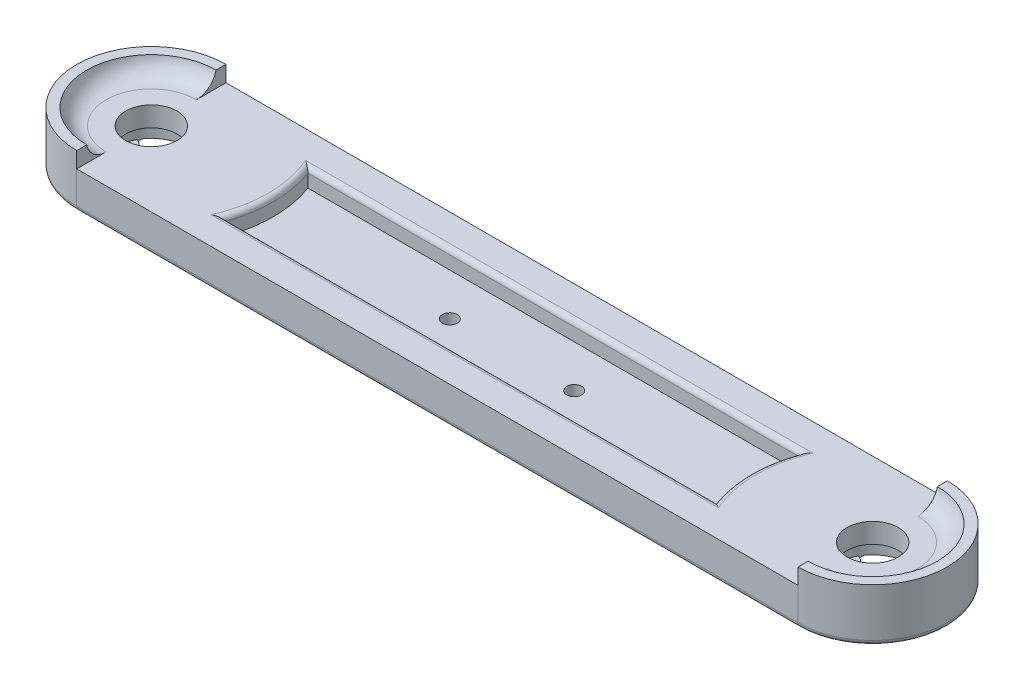
SolidWorks part; units mm, degrees
ref_plane "Alzado" through (0, 0, 0) normal (0, 0, 1) x (1, 0, 0)
ref_plane "Planta" through (0, 0, 0) normal (0, 1, 0) x (1, 0, 0)
ref_plane "Vista lateral" through (0, 0, 0) normal (1, 0, 0) x (0, 0, -1)
sketch "Croquis1" plane through (0, 0, 0) normal (0, 1, 0) x (1, 0, 0)
  line L0 (72.5, 0) -> (-72.5, 0) construction
  line L1 (-72.5, 15) -> (-72.5, -15) construction
  line L2 (-72.5, 0) -> (-80, 12.9904) construction
  line L3 (-72.5, 0) -> (-80, -12.9904) construction
  line L4 (0, 0) -> (0, 15) construction
  line L5 (-72.5, 15) -> (72.5, 15)
  line L6 (-72.5, -15) -> (72.5, -15)
  circle A0 centre (-72.5, 0) radius 15
  circle A2 centre (-72.5, 0) radius 5.15
  circle A3 centre (72.5, 0) radius 15
  circle A4 centre (72.5, 0) radius 5.15
  point P4 (0, 0)
  dimension "D3" = 30
  dimension "D4" = 10.3
  dimension "D1" = 145
  dimension "D2" = 30
  dimension "D5" = 30
  dimension "D6" = 15
extrude "Saliente-Extruir1" add sketch "Croquis1" along normal blind 7.5 contours A0 A2 | L6 A3 L5 A0 | A3 A4 region at (0, 0, 0) region at (-62.1934, 0, -10.3066) region at (82.8066, 0, -10.3066)
sketch "Croquis2" plane through (0, 0, 0) normal (0, -1, 0) x (1, 0, 0)
  line L0 (-72.5, 5.15) -> (-72.5, -5.15) construction
  line L1 (-72.5, 0) -> (-72.5, 5.15) construction
  line L2 (-72.5, 0) -> (-72.5, -5.15) construction
  line L3 (-72.5, 0) -> (-72.5, -5.15) construction
  line L4 (-72.5, 0) -> (-72.5, 5.15) construction
  line L5 (-72.5, 5.15) -> (-72.5, 7.5)
  line L6 (-72.5, 5.15) -> (-72.5, 7.5)
  line L7 (-72.5, -5.15) -> (-72.5, -7.5)
  line L8 (-72.5, -5.15) -> (-72.5, -7.5)
  line L9 (0, 0) -> (0, 15) construction
  line L10 (-72.5, 15) -> (72.5, 15) construction
  line L11 (72.5, -5.15) -> (72.5, -7.5)
  line L12 (72.5, -5.15) -> (72.5, -7.5)
  line L13 (72.5, 5.15) -> (72.5, 7.5)
  line L14 (72.5, 5.15) -> (72.5, 7.5)
  circle A0 centre (-72.5, 0) radius 5.15 construction
  circle A1 centre (-72.5, 0) radius 5.15
  arc A2 (-72.5, 7.5) -> (-72.5, -7.5) centre (-72.5, 0) ccw
  arc A3 (-72.5, -7.5) -> (-72.5, 7.5) centre (-72.5, 0) ccw
  arc A4 (72.5, -7.5) -> (72.5, 7.5) centre (72.5, 0) cw
  circle A5 centre (72.5, 0) radius 5.15
  arc A6 (72.5, 7.5) -> (72.5, -7.5) centre (72.5, 0) cw
  circle M6 centre (-72.5, 0) radius 5.15
  circle M11 centre (72.5, 0) radius 5.15
  dimension "D3" = 15
  dimension "D1" = 0
  dimension "D2" = 0
extrude "Cortar-Extruir1" cut sketch "Croquis2" against normal blind 3.5 contours L6 A2 L7 M6 | L8 A3 L5 M6 | A4 L12 L13 M11 | A6 L14 L11 M11 region at (-77.8177, 0, 0) region at (-72.3323, 0, 6.325) region at (76.2602, 0, -3.7602) region at (72.3323, 0, -6.325)
sketch "Croquis3" plane through (0, 7.5, 0) normal (0, 1, 0) x (1, 0, 0)
  line L0 (-87.5, 0) -> (87.5, 0) construction
  line L1 (-17.5, 25) -> (-23.5102, 25)
  line L2 (-17.5, -25) -> (-23.5102, -25)
  line L3 (0, 0) -> (0, 30) construction
  line L4 (17.5, -25) -> (23.5102, -25)
  line L5 (12.5, -30) -> (-12.5, -30)
  line L6 (17.5, -25) -> (17.5, 25)
  line L7 (12.5, 30) -> (-12.5, 30)
  line L8 (-17.5, -25) -> (-17.5, 25)
  line L9 (17.5, -30) -> (-17.5, 30) construction
  line L10 (17.5, 30) -> (-17.5, -30) construction
  line L11 (17.5, 25) -> (23.5102, 25)
  arc A0 (-72.5, 15) -> (-72.5, -15) centre (-72.5, 0) ccw construction
  arc A1 (72.5, -15) -> (72.5, 15) centre (72.5, 0) ccw construction
  arc A2 (12.5, -30) -> (17.5, -25) centre (12.5, -25) ccw
  arc A3 (-12.5, -30) -> (-17.5, -25) centre (-12.5, -25) cw
  arc A4 (12.5, 30) -> (17.5, 25) centre (12.5, 25) cw
  arc A5 (-12.5, 30) -> (-17.5, 25) centre (-12.5, 25) ccw
  circle A6 centre (-72.5, 0) radius 5.15 construction
  circle A7 centre (-72.5, 0) radius 5.15 construction
  arc A10 (-23.5102, -25) -> (-23.5102, 25) centre (-72.5, 0) ccw
  arc A11 (23.5102, -25) -> (23.5102, 25) centre (72.5, 0) cw
  point P14 (0, 0)
  point P18 (0, 0)
  dimension "D3" = 5
  dimension "D1" = 25
  dimension "D2" = 60
sketch "Croquis9" plane through (0, 7.5, 0) normal (0, 1, 0) x (1, 0, 0)
  line L2 (-72.5, 15) -> (-72.5, 13)
  line L6 (-72.5, -13) -> (-72.5, -15)
  line L7 (72.5, 15) -> (72.5, 13)
  line L8 (-72.5, -15) -> (72.5, -15)
  line L9 (72.5, 15) -> (-72.5, 15)
  line L12 (72.5, -13) -> (72.5, -15)
  arc A5 (-72.5, 13) -> (-72.5, -13) centre (-72.5, 0) ccw
  arc A6 (72.5, -13) -> (72.5, 13) centre (72.5, 0) ccw
  arc A7 (-72.5, 15) -> (-72.5, -15) centre (-72.5, 0) ccw
  arc A8 (72.5, -15) -> (72.5, 15) centre (72.5, 0) ccw
  arc A9 (-72.5, 15) -> (-72.5, -15) centre (-72.5, 0) ccw
  arc A10 (72.5, -15) -> (72.5, 15) centre (72.5, 0) ccw
  dimension "D1" = 0
  dimension "D2" = 2
extrude "Saliente-Extruir6" add sketch "Croquis9" along normal blind 3.2
sketch "Croquis13" plane through (0, 7.5, 0) normal (0, 1, 0) x (1, 0, 0)
  line L0 (0, 0) -> (-47.5, 0) construction
  line L1 (-47.5, 0) -> (-72.5, 0) construction
  line L2 (0, 8) -> (0, -8) construction
  line L3 (48.8146, 8) -> (-48.8146, 8) construction
  line L4 (48.8146, -8) -> (-48.8146, -8) construction
  line L5 (49.5217, -8.5) -> (-49.5217, -8.5)
  line L6 (49.5217, 8.5) -> (-49.5217, 8.5)
  circle A0 centre (-72.5, 0) radius 25 construction
  arc A1 (-48.8146, 8) -> (-48.8146, -8) centre (-72.5, 0) cw construction
  arc A2 (48.8146, 8) -> (48.8146, -8) centre (72.5, 0) ccw construction
  circle A3 centre (-12.5, 0) radius 1.5
  circle A4 centre (12.5, 0) radius 1.5
  arc A5 (-49.5217, 8.5) -> (-49.5217, -8.5) centre (-72.5, 0) cw
  arc A6 (49.5217, 8.5) -> (49.5217, -8.5) centre (72.5, 0) ccw
  circle A7 centre (-72.5, 0) radius 5.15 construction
  circle A8 centre (-72.5, 0) radius 5.15 construction
  point P8 (0, 0)
  point P14 (-12.5, 0)
  dimension "D5" = 3
  dimension "D1" = 12.5
  dimension "D2" = 25
  dimension "D3" = 16
  dimension "D6" = 0.5
extrude "Cortar-Extruir2" cut sketch "Croquis13" against normal blind 3.6
fillet "Redondeo1" radius 4 2 edges at (85.5, 7.5, 0) (-85.5, 7.5, 0)
fillet "Redondeo2" radius 1 4 edges at (0, 0, -15) (87.5, 0, 0) (0, 0, 15) (-87.5, 0, 0)
fillet "Redondeo3" radius 1 4 edges at (0, 7.5, 8.5) (0, 7.5, -8.5) (-48, 7.5, 0) (48, 7.5, 0)
sketch "Croquis14" plane through (0, 0, 0) normal (0, -1, 0) x (1, 0, 0)
  line L2 (-72.5, 7.3837) -> (-72.5, -6.4282) construction
  line L5 (-78.9344, 3.6025) -> (-81.186, 4.2058)
  line L6 (55, 0) -> (-55, 0) construction
  line L7 (-78.9344, -3.6025) -> (-81.186, -4.2058)
  line L8 (-66.0656, -3.6025) -> (-63.814, -4.2058)
  line L9 (-66.0656, 3.6025) -> (-63.814, 4.2058)
  circle A0 centre (-72.5, 0) radius 7.5 construction
  arc A1 (-81.186, 4.2058) -> (-81.186, -4.2058) centre (-73.5, 0) ccw
  circle A4 centre (-72.5, 0) radius 5.15 construction
  circle A5 centre (-72.5, 0) radius 7.5 construction
  arc A6 (-77.5074, 1.2033) -> (-77.5074, -1.2033) centre (-72.5, 0) ccw
  arc A7 (-79.0597, 3.636) -> (-65, 0) centre (-72.5, 0) ccw construction
  arc A9 (-72.5, 14) -> (-72.5, -14) centre (-72.5, 0) ccw construction
  arc A14 (-77.5074, -1.2033) -> (-78.9344, -3.6025) centre (-79.4521, -1.6706) cw
  arc A15 (-77.5074, 1.2033) -> (-78.9344, 3.6025) centre (-79.4521, 1.6706) ccw
  arc A16 (-65.9403, 3.636) -> (-80, 0) centre (-72.5, 0) cw construction
  arc A17 (-67.4926, 1.2033) -> (-66.0656, 3.6025) centre (-65.5479, 1.6706) cw
  arc A18 (-67.4926, -1.2033) -> (-66.0656, -3.6025) centre (-65.5479, -1.6706) ccw
  arc A19 (-67.4926, 1.2033) -> (-67.4926, -1.2033) centre (-72.5, 0) cw
  arc A20 (-63.814, 4.2058) -> (-63.814, -4.2058) centre (-71.5, 0) cw
  point P22 (-76.686, -3)
  point P25 (-76.686, 3)
  point P37 (-68.314, 3)
  point P38 (-68.314, -3)
  dimension "D4" = 15
  dimension "D3" = 1
  dimension "D5" = 2
  dimension "D2" = 3
  dimension "D1" = 4.5
extrude "Saliente-Extruir7" add sketch "Croquis14" along normal blind 2
fillet "Redondeo5" radius 1 12 edges at (-64.8772, 0, -3.9209) (-64.8772, 0, 3.9209) (-80.1228, 0, 3.9209) (-80.1228, 0, -3.9209) (-63.814, -1, -4.2058) (-62.7386, -2, 0) (-63.814, -1, 4.2058) (-62.7386, 0, 0) (-81.186, -1, 4.2058) (-82.2614, -2, 0) (-81.186, -1, -4.2058) (-82.2614, 0, 0)
mirror "Simetría1" about plane through (0, 0, 0) normal (1, 0, 0) of "Redondeo5", "Saliente-Extruir7"
extrude "Cortar-Extruir3" cut sketch "Croquis13<2>" against normal through all contours A3 | A4 region at (-12.5, 7.5, 0) region at (12.5, 7.5, 0)
sketch "Croquis13<2>" plane through (0, 7.5, 0) normal (0, 1, 0) x (1, 0, 0) same geometry as "Croquis13"
